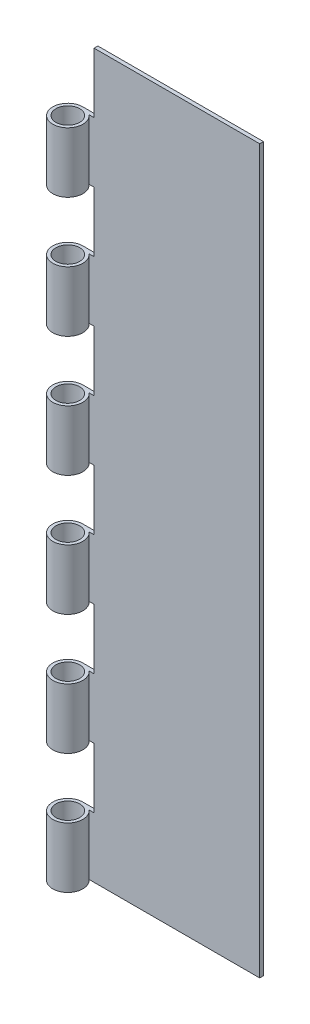
SolidWorks part; units mm, degrees
ref_plane "Front Plane" through (0, 0, 0) normal (0, 0, 1) x (1, 0, 0)
ref_plane "Top Plane" through (0, 0, 0) normal (0, 1, 0) x (1, 0, 0)
ref_plane "Right Plane" through (0, 0, 0) normal (1, 0, 0) x (0, 0, -1)
sketch "Sketch1" plane through (0, 0, 0) normal (0, 0, 1) x (1, 0, 0)
  line L1 (-40.8445, 195.8032) -> (35.3555, 195.8032)
  line L2 (-40.8445, 195.8032) -> (-40.8445, -108.9968)
  line L3 (-40.8445, -108.9968) -> (35.3555, -108.9968)
  line L4 (35.3555, 195.8032) -> (35.3555, -108.9968)
  dimension "D1" = 304.8
  dimension "D2" = 76.2
extrude "Boss-Extrude1" add sketch "Sketch1" along normal blind 1.5875
sketch "Sketch2" plane through (0, 195.8032, 0) normal (0, 1, 0) x (1, 0, 0)
  line L1 (-40.8445, -1.5875) -> (-40.8445, 0) construction
  line L2 (35.3555, 0) -> (-40.8445, 0) construction
  circle A0 centre (-40.8445, -6.35) radius 6.35
  dimension "D1" = 12.7
extrude "Boss-Extrude2" add sketch "Sketch2" against normal up to surface (304.8 mm away) up to face at (-2.7445, -108.9968, 0.7937)
sketch "Sketch5" plane through (0, 195.8032, 0) normal (0, 1, 0) x (1, 0, 0)
  circle A0 centre (-40.8445, -6.35) radius 5.0201
  arc A1 (-40.8445, 0) -> (-36.6444, -1.5875) centre (-40.8445, -6.35) ccw construction
extrude "Cut-Extrude1" cut sketch "Sketch5" against normal up to next
sketch "Sketch6" plane through (0, 0, 1.5875) normal (0, 0, 1) x (1, 0, 0)
  line L0 (-34.4945, -108.9968) -> (-34.4945, 195.8032) construction
  line L1 (-65.7484, 195.8032) -> (-34.4945, 195.8032)
  line L2 (-65.7484, 195.8032) -> (-65.7484, 170.4032)
  line L3 (-65.7484, 170.4032) -> (-34.4945, 170.4032)
  line L4 (-34.4945, 195.8032) -> (-34.4945, 170.4032)
  line L5 (-65.7484, 145.0032) -> (-34.4945, 145.0032)
  line L6 (-65.7484, 145.0032) -> (-65.7484, 119.6032)
  line L7 (-65.7484, 119.6032) -> (-34.4945, 119.6032)
  line L8 (-34.4945, 145.0032) -> (-34.4945, 119.6032)
  line L9 (-65.7484, 94.2032) -> (-34.4945, 94.2032)
  line L10 (-65.7484, 94.2032) -> (-65.7484, 68.8032)
  line L11 (-65.7484, 68.8032) -> (-34.4945, 68.8032)
  line L12 (-34.4945, 94.2032) -> (-34.4945, 68.8032)
  line L13 (-65.7484, 43.4032) -> (-34.4945, 43.4032)
  line L14 (-65.7484, 43.4032) -> (-65.7484, 18.0032)
  line L15 (-65.7484, 18.0032) -> (-34.4945, 18.0032)
  line L16 (-34.4945, 43.4032) -> (-34.4945, 18.0032)
  line L17 (-70.0927, -7.3968) -> (-34.4945, -7.3968)
  line L18 (-70.0927, -7.3968) -> (-70.0927, -32.7968)
  line L19 (-70.0927, -32.7968) -> (-34.4945, -32.7968)
  line L20 (-34.4945, -7.3968) -> (-34.4945, -32.7968)
  line L21 (-63.5777, -58.1968) -> (-34.4945, -58.1968)
  line L22 (-63.5777, -58.1968) -> (-63.5777, -83.5968)
  line L23 (-63.5777, -83.5968) -> (-34.4945, -83.5968)
  line L24 (-34.4945, -58.1968) -> (-34.4945, -83.5968)
  line L25 (-34.4945, 195.8032) -> (-47.1945, 195.8032) construction
  line L26 (-34.4945, 170.4032) -> (-34.4945, 145.0032) construction
  line L27 (-34.4945, 119.6032) -> (-34.4945, 94.2032) construction
  line L28 (-34.4945, 68.8032) -> (-34.4945, 43.4032) construction
  line L29 (-34.4945, 18.0032) -> (-34.4945, -7.3968) construction
  line L30 (-34.4945, -32.7968) -> (-34.4945, -58.1968) construction
  line L31 (-34.4945, -83.5968) -> (-34.4945, -108.9968) construction
extrude "Cut-Extrude2" cut sketch "Sketch6" against normal blind 22.4155 and the other way blind 22.4155
